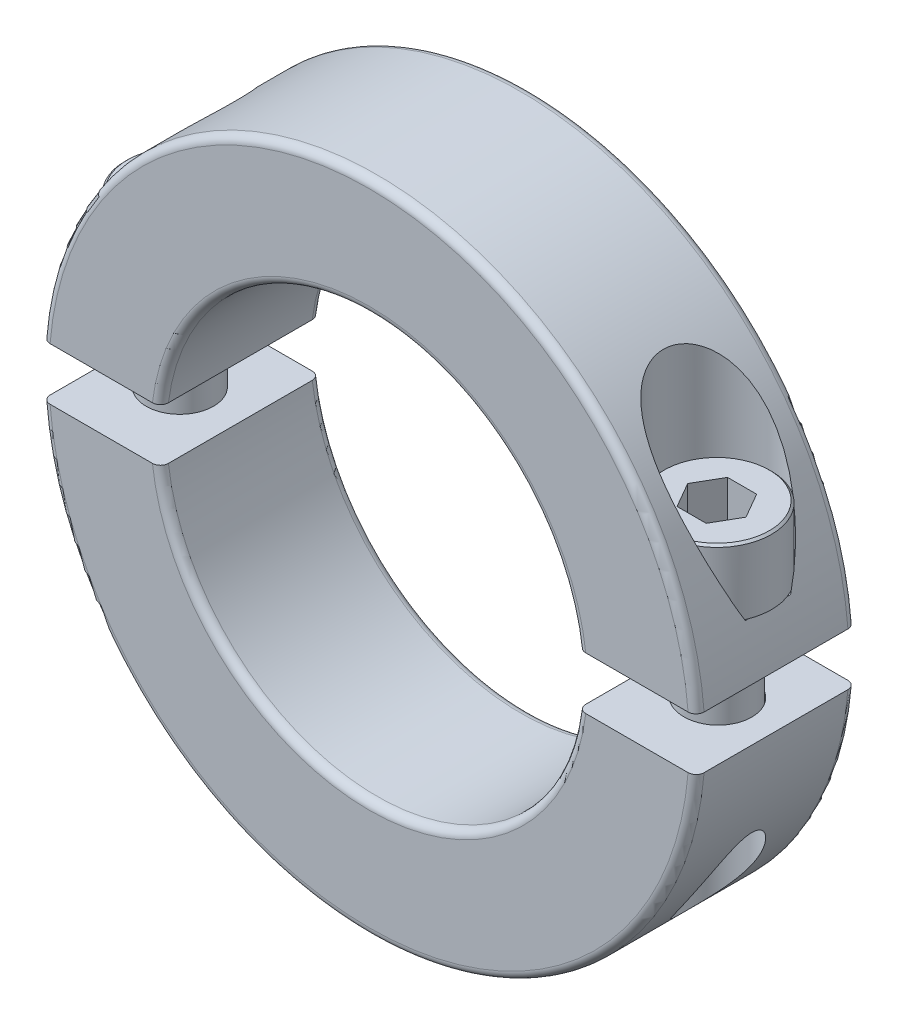
SolidWorks part; units mm, degrees
ref_plane "Front Plane" through (0, 0, 0) normal (0, 0, 1) x (1, 0, 0)
ref_plane "Top Plane" through (0, 0, 0) normal (0, 1, 0) x (1, 0, 0)
ref_plane "Right Plane" through (0, 0, 0) normal (1, 0, 0) x (0, 0, -1)
sketch "Sketch1" plane through (0, 0, 0) normal (0, 0, 1) x (1, 0, 0)
  line L0 (-39, 0) -> (-25, 0) construction
  line L1 (-38.875, 3.12) -> (-24.8045, 3.12)
  line L2 (-38.875, -3.12) -> (-24.8045, -3.12)
  line L3 (24.8045, 3.12) -> (38.875, 3.12)
  line L4 (24.8045, -3.12) -> (38.875, -3.12)
  line L5 (0, 0) -> (0, 39) construction
  line L6 (-32, 0) -> (-32, 3.12) construction
  line L7 (-32, 0) -> (-32, -3.12) construction
  line L8 (31.8398, 3.12) -> (31.8398, -3.12) construction
  circle A0 centre (0, 0) radius 39 construction
  circle A1 centre (0, 0) radius 25 construction
  arc A4 (-24.8045, -3.12) -> (24.8045, -3.12) centre (0, 0) ccw
  arc A5 (-38.875, -3.12) -> (38.875, -3.12) centre (0, 0) ccw
  arc A6 (24.8045, 3.12) -> (-24.8045, 3.12) centre (0, 0) ccw
  arc A7 (38.875, 3.12) -> (-38.875, 3.12) centre (0, 0) ccw
  point P4 (39, 0)
  point P14 (-39, 0)
  point P19 (-25, 0)
  point P21 (25, 0)
  dimension "Bore Dia" = 50
  dimension "OD" = 78
  dimension "Separation" = 6.24
  dimension "D1" = 63.8398
extrude "Extrude1" add sketch "Sketch1" along normal mid plane 19
fillet "Fillet1" radius 0.95 4 edges at (0, 25, 9.5) (0, 25, -9.5) (0, 39, -9.5) (0, 39, 9.5)
fillet "Fillet2" radius 0.95 4 edges at (0, -39, 9.5) (0, -25, 9.5) (0, -25, -9.5) (0, -39, -9.5)
sketch "Sketch2" plane through (0, 0, 0) normal (0, 1, 0) x (1, 0, 0)
  line L0 (0, 9.5) -> (0, -9.5) construction
  line L3 (0, 0) -> (-25, 0) construction
  line L4 (-25, 0) -> (-39, 0) construction
  line L7 (-32, 9.5) -> (-32, -9.5) construction
  line L8 (-32.1905, 9.5) -> (-31.8095, 9.5)
  line L9 (-37.9219, -9.5) -> (37.9219, -9.5) construction
  line L10 (-39, 0) -> (-25, 0) construction
  line L11 (37.9219, 9.5) -> (-37.9219, 9.5) construction
  arc A0 (-32.1905, 9.5) -> (-31.8095, 9.5) centre (-32, 9.5) ccw
  point P16 (-32, 0)
  dimension "D2" = 0.1905
revolve "Cut-Revolve1" cut sketch "Sketch2" angle 360 about L0
sketch "Sketch3" plane through (0, 0, 0) normal (0, 0, 1) x (1, 0, 0)
  line L0 (-32, 39) -> (-25.4975, 39)
  line L1 (-25.4975, 39) -> (-25.4975, 9.12)
  line L2 (-25.4975, 9.12) -> (-28, 9.12)
  line L3 (-28, 9.12) -> (-28, -39)
  line L4 (-28, -39) -> (-32, -39)
  line L5 (-32, -39) -> (-32, 39)
  line L7 (-32, 39) -> (-32, 45.5025) construction
  line L8 (-25.4975, 39) -> (0, 39) construction
  line L9 (0, -39) -> (-28, -39) construction
  line L10 (-39, 0) -> (-25, 0) construction
  line L11 (-38.875, 3.12) -> (-24.8045, 3.12) construction
  line L12 (0, 0) -> (0, -39) construction
  line L13 (-32, 0) -> (-32, -3.12) construction
  circle A0 centre (0, 0) radius 39 construction
  circle A2 centre (0, 0) radius 25 construction
  arc A4 (-38.875, -3.12) -> (38.875, -3.12) centre (0, 0) ccw construction
  dimension "D3" = 6
  dimension "D1" = 13.005
revolve "Cut-Revolve2" cut sketch "Sketch3" angle 360 about L5
mirror "Mirror1" about plane through (0, 0, 0) normal (1, 0, 0) of "Cut-Revolve2"
sketch "Sketch8" plane through (0, 9.12, 0) normal (0, 1, 0) x (1, 0, 0)
  circle A0 centre (32, 0) radius 4 construction
  circle A1 centre (32, 0) radius 4
extrude "Cut-Extrude3" cut sketch "Sketch8" against normal through all
sketch "Sketch4" plane through (0, 0, 0) normal (0, 0, 1) x (1, 0, 0)
  line L0 (-32, 17.12) -> (-25.5, 17.12)
  line L2 (-25.5, 17.12) -> (-25.5, 9.12)
  line L3 (-25.5, 9.12) -> (-28, 9.12)
  line L4 (-28, 9.12) -> (-28, -15.88)
  line L5 (-28, 9.12) -> (-28, -39) construction
  line L6 (-28, -15.88) -> (-32, -15.88)
  line L7 (-32, -39) -> (-32, 39) construction
  line L8 (-32, -15.88) -> (-32, 17.12)
  line L9 (-28, -15.88) -> (-36, -15.88) construction
  line L10 (-32, 17.12) -> (-32, 23.62) construction
  dimension "Screw Lg" = 25
  dimension "Head Dia" = 13
revolve "Revolve1" add sketch "Sketch4" angle 360 about L8
sketch "Sketch5" plane through (0, 17.12, 0) normal (0, 1, 0) x (-1, 0, 0)
  line L1 (33.7321, -3) -> (35.4641, 0)
  line L2 (35.4641, 0) -> (33.7321, 3)
  line L3 (33.7321, 3) -> (30.2679, 3)
  line L4 (30.2679, 3) -> (28.5359, 0)
  line L5 (28.5359, 0) -> (30.2679, -3)
  line L6 (30.2679, -3) -> (33.7321, -3)
  circle A0 centre (32, 0) radius 3 construction
  dimension "Hex" = 6
extrude "Cut-Extrude2" cut sketch "Sketch5" against normal blind 6
chamfer "Chamfer1" distance 0.254 angle 45 1 edges at (-32, 17.12, -6.5)
sketch "Sketch6" plane through (0, -15.88, 0) normal (0, -1, 0) x (1, 0, 0)
  circle A0 centre (-32, 0) radius 4 construction
  circle A1 centre (-32, 0) radius 4
  point P3 (-36, 0)
curve "Helix/Spiral1" [suppressed] pitch 1.25 height 25 turns 20 parameters "Height"=25, "Pitch"=1.25
sketch "Sketch7" plane through (0, 0, 0) normal (0, 0, 1) x (1, 0, 0)
  line L0 (-36.1353, -15.8019) -> (-36.1353, -17.0519) construction
  line L1 (-36.1353, -17.0519) -> (-35.0528, -16.4269) construction
  line L2 (-35.0528, -16.4269) -> (-36.1353, -15.8019) construction
  line L3 (-36.1353, -16.4269) -> (-36, -16.4269) construction
  line L4 (-35.0528, -16.4269) -> (-35.1881, -16.4269) construction
  line L5 (-35.1881, -16.3488) -> (-35.1881, -16.505)
  line L6 (-36, -16.9738) -> (-36, -15.88) construction
  line L7 (-35.1881, -16.3488) -> (-36.0677, -15.8409)
  line L8 (-36.0677, -15.8409) -> (-36.0677, -17.0128)
  line L9 (-36.0677, -17.0128) -> (-35.1881, -16.505)
  point P10 (-36.0677, -16.4269)
  dimension "D1" = 1.25
  dimension "D2" = 0.1562
chamfer "Chamfer2" distance 1.25 angle 45 1 edges at (-32, -15.88, -4)
sweep "Cut-Sweep1" [suppressed] cut profiles "Sketch7" path "Helix/Spiral1"
pattern_linear "LPattern1" count 2 spacing 63.8398 along (1, 0, 0) of bodies 149 162
equation "\"D1@Sketch3\" = \"Head Dia@Sketch4\"+.005"
equation "\"D1@Cut-Extrude2\" =\"Hex@Sketch5\""
equation "\"D1@Fillet1\" = \"Width@Extrude1\"*.05"
equation "\"D1@Fillet2\" = \"D1@Fillet1\""
equation "\"Height@Helix/Spiral1\" = \"Screw Lg@Sketch4\""
equation "\"D1@Sketch7\" = \"Pitch@Helix/Spiral1\""
equation "\"D2@Sketch7\" = \"D1@Sketch7\"/8"
equation "\"D1@Chamfer2\" = \"Pitch@Helix/Spiral1\""
equation "\"D3@Sketch3\" = \"Screw Dia@Sketch3\"*.750"
equation "\"D3@LPattern1\" = \"D1@Sketch1\""
